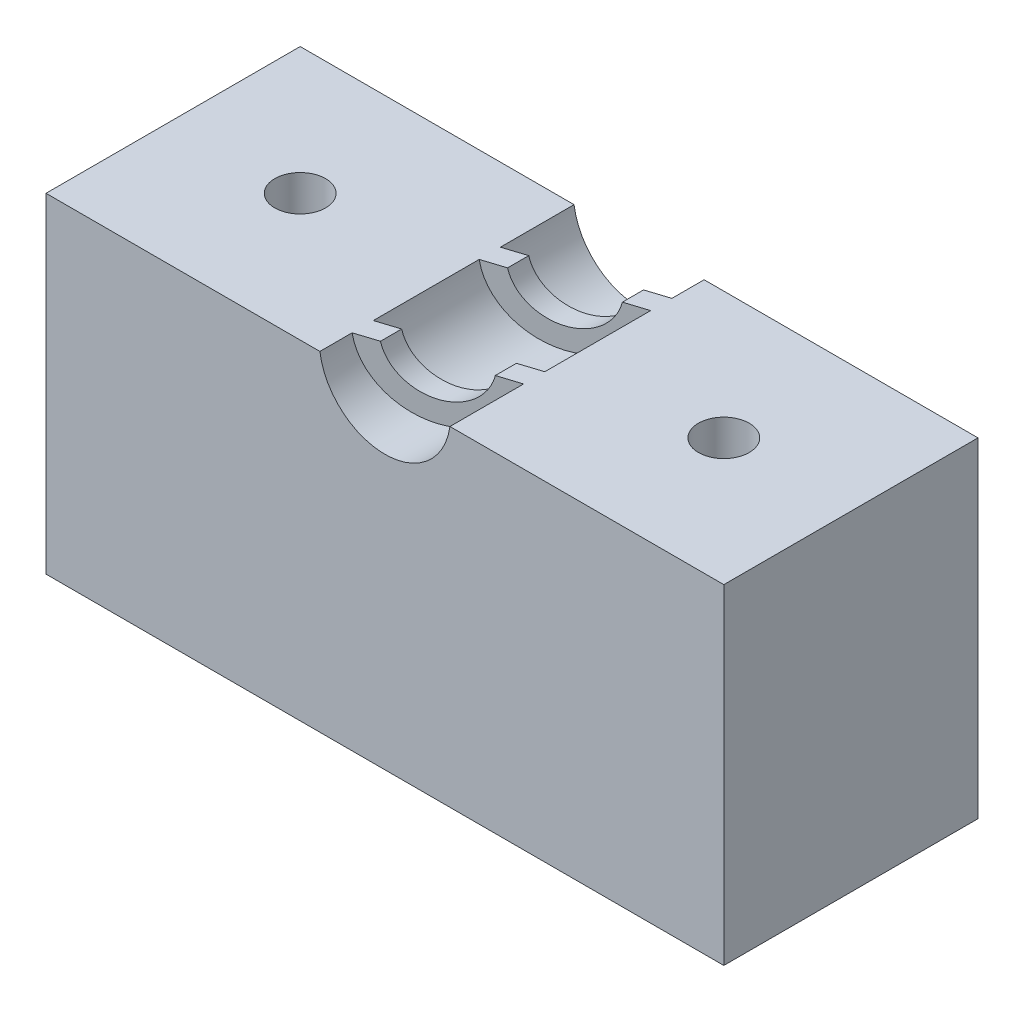
SolidWorks part; units mm, degrees
ref_plane "前视基准面" through (0, 0, 0) normal (0, 0, 1) x (1, 0, 0)
ref_plane "上视基准面" through (0, 0, 0) normal (0, 1, 0) x (1, 0, 0)
ref_plane "右视基准面" through (0, 0, 0) normal (1, 0, 0) x (0, 0, -1)
other "Configuration Table"
sketch "草图1" plane through (0, 0, 0) normal (0, 0, 1) x (1, 0, 0)
  line L1 (-8, -8) -> (8, -8)
  line L2 (-8, -8) -> (-8, 8)
  line L3 (-8, 8) -> (8, 8)
  line L4 (8, -8) -> (8, 8)
  line L5 (-8, -8) -> (8, 8) construction
  line L6 (-8, 8) -> (8, -8) construction
  circle A0 centre (0, 0) radius 1.55
  point P0 (0, 0)
  dimension "D3" = 3.1
  dimension "D1" = 16
  dimension "D2" = 16
extrude "凸台-拉伸1" add sketch "草图1" along normal mid plane 6
sketch "草图6" plane through (0, 0, 0) normal (0, 1, 0) x (1, 0, 0)
  line L0 (-1.55, -3) -> (1.55, -3) construction
  line L1 (1.55, 3) -> (-1.55, 3) construction
  line L2 (-1.55, -3) -> (1.55, -3)
  line L3 (1.55, 3) -> (-1.55, 3)
  line L4 (-1.55, 3) -> (-1.55, -3)
  line L5 (1.55, -3) -> (1.55, 3)
  line L6 (-1.55, 0.7565) -> (1.55, 1.7435)
  line L7 (1.55, 1.7435) -> (1.55, 2.2435)
  line L8 (1.55, 2.2435) -> (-1.55, 1.2565)
  line L9 (-1.55, -1.7435) -> (1.55, -0.7565)
  line L10 (-1.55, -2.2435) -> (1.55, -1.2565)
  line L11 (-2.0945, -0.6668) -> (3.135, 0.9981) construction
  line L12 (-3.1004, 0) -> (4.2723, 0) construction
  dimension "D1" = 2.5
  dimension "D2" = 0.5
  dimension "D3" = 0.5
  dimension "D4" = 17.66
extrude "凸台-拉伸2" add sketch "草图6" against normal up to surface (8 mm away) contours L4 L10 L5 L9 | L5 L8 L4 L6 region at (0, 0, 1.5) region at (0, 0, -1.5) up to face at (0, -8, 0)
sketch "草图7" plane through (0, 0, 0) normal (0, 0, 1) x (1, 0, 0)
  line L0 (0, 0) -> (-1.0279, -0.2141)
  line L1 (0, 0) -> (1.0279, -0.2141)
  line L2 (-1.0279, -0.2141) -> (-8, -0.2141)
  line L3 (1.0279, -0.2141) -> (8, -0.2141)
  line L6 (8, -8) -> (8, 8)
  line L7 (-8, -8) -> (8, -8)
  line L8 (-8, 8) -> (-8, -8)
  line L9 (8, 8) -> (-8, 8)
  line L10 (8, -8) -> (8, 8)
  line L11 (-8, -8) -> (8, -8)
  line L12 (-8, 8) -> (-8, -8)
  line L13 (8, 8) -> (-8, 8)
  circle A0 centre (0, 0) radius 1.05
  dimension "D1" = 2.1
  dimension "D2" = 0
  dimension "D3" = 156.47
extrude "切除-拉伸2" cut sketch "草图7" against normal through all both and the other way through all contours A0 L3 L10 L13 L12 L2 | L1 A0 L0 | L0 A0 L1 region at (0, -0.5019, 0) region at (0, 0.3858, 0) region at (0, 3.953, 0)
sketch "草图8" plane through (0, 0, 0) normal (0, 1, 0) x (1, 0, 0)
  line L0 (0, 5.5834) -> (0, -5.0797) construction
  circle A0 centre (-5, 0) radius 0.6
  circle A1 centre (5, 0) radius 0.6
  dimension "D2" = 1.2
  dimension "D3" = 10
extrude "切除-拉伸3" cut sketch "草图8" against normal through all
equation "\"x\"=0.8094"
